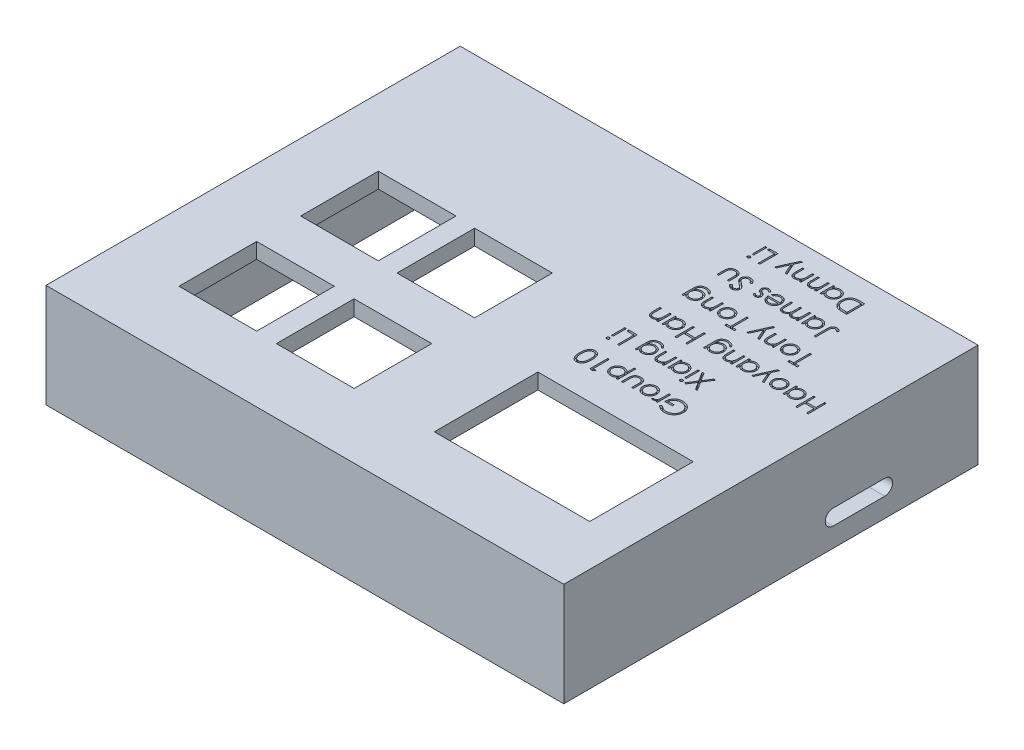
SolidWorks part; units mm, degrees
ref_plane "Front Plane" through (0, 0, 0) normal (0, 0, 1) x (1, 0, 0)
ref_plane "Top Plane" through (0, 0, 0) normal (0, 1, 0) x (1, 0, 0)
ref_plane "Right Plane" through (0, 0, 0) normal (1, 0, 0) x (0, 0, -1)
sketch "Sketch1" plane through (0, 0, 0) normal (0, 1, 0) x (1, 0, 0)
  line L1 (-50, -40) -> (50, -40)
  line L2 (-50, -40) -> (-50, 40)
  line L3 (-50, 40) -> (50, 40)
  line L4 (50, -40) -> (50, 40)
  line L5 (-50, -40) -> (50, 40) construction
  line L6 (-50, 40) -> (50, -40) construction
  point P0 (0, 0)
  dimension "D1" = 100
  dimension "D2" = 80
extrude "Boss-Extrude1" add sketch "Sketch1" along normal blind 20
sketch "Sketch2" plane through (0, 0, 0) normal (0, -1, 0) x (1, 0, 0)
  line L0 (-50, 40) -> (50, 40) construction
  line L1 (-47, 37) -> (47, 37)
  line L2 (-47, 37) -> (-47, -37)
  line L3 (-47, -37) -> (47, -37)
  line L4 (47, 37) -> (47, -37)
  line L5 (-47, 37) -> (47, -37) construction
  line L6 (-47, -37) -> (47, 37) construction
  line L7 (-50, -40) -> (-50, 40) construction
  point P0 (0, 0)
  dimension "D1" = 3
  dimension "D2" = 3
extrude "Cut-Extrude1" cut sketch "Sketch2" against normal blind 17
sketch "Sketch7" plane through (50, 0, 0) normal (1, 0, 0) x (0, 0, -1)
  line L0 (17, 5.2318) -> (17, 2.8813)
  line L1 (40, 20) -> (40, 0) construction
  line L2 (17, 5.2318) -> (22, 5.2318)
  line L3 (17, 5.2318) -> (12, 5.2318)
  line L4 (22, 5.2318) -> (12, 5.2318) construction
  line L5 (22, 3.7318) -> (12, 3.7318)
  line L6 (22, 6.7318) -> (12, 6.7318)
  arc A0 (22, 3.7318) -> (22, 6.7318) centre (22, 5.2318) ccw
  arc A1 (12, 6.7318) -> (12, 3.7318) centre (12, 5.2318) ccw
  point P2 (17, 4.0565)
  point P5 (17, 5.2318)
  dimension "D1" = 23
  dimension "D2" = 5
  dimension "D3" = 5
  dimension "D4" = 1.5
extrude "Cut-Extrude2" cut sketch "Sketch7" against normal blind 17 contours L6 A1 L5 A0
sketch "Sketch10" plane through (0, 20, 0) normal (0, 1, 0) x (1, 0, 0)
  line L0 (-50, -40) -> (50, -40) construction
  line L1 (42, -7) -> (12, -7)
  line L2 (42, -7) -> (42, -27)
  line L3 (42, -27) -> (12, -27)
  line L4 (12, -7) -> (12, -27)
  line L5 (42, -7) -> (12, -27) construction
  line L6 (42, -27) -> (12, -7) construction
  line L7 (50, -40) -> (50, 40) construction
  point P0 (27, -17)
  dimension "D1" = 23
  dimension "D2" = 23
  dimension "D3" = 30
  dimension "D4" = 20
extrude "Cut-Extrude3" cut sketch "Sketch10" against normal blind 17
sketch "Sketch12" plane through (0, 20, 0) normal (0, 1, 0) x (1, 0, 0)
  line L0 (12, -7) -> (12, -27) construction
  line L1 (-18, -27.5) -> (-3, -27.5)
  line L2 (-18, -27.5) -> (-18, -12.5)
  line L3 (-18, -12.5) -> (-3, -12.5)
  line L4 (-3, -27.5) -> (-3, -12.5)
  line L5 (-18, -27.5) -> (-3, -12.5) construction
  line L6 (-18, -12.5) -> (-3, -27.5) construction
  line L7 (-50, -40) -> (50, -40) construction
  point P0 (-10.5, -20)
  dimension "D1" = 15
  dimension "D2" = 20
  dimension "D3" = 15
  dimension "D4" = 15
extrude "Cut-Extrude4" cut sketch "Sketch12" against normal blind 17
sketch "Sketch13" plane through (0, 20, 0) normal (0, 1, 0) x (1, 0, 0)
  line L1 (-37, -27.3155) -> (-22, -27.3155)
  line L2 (-37, -27.3155) -> (-37, -12.3155)
  line L3 (-37, -12.3155) -> (-22, -12.3155)
  line L4 (-22, -27.3155) -> (-22, -12.3155)
  line L5 (-37, -27.3155) -> (-22, -12.3155) construction
  line L6 (-37, -12.3155) -> (-22, -27.3155) construction
  line L7 (-18, -27.5) -> (-3, -27.5) construction
  point P0 (-29.5, -19.8155)
  point P7 (-10.5, -27.5)
  dimension "D1" = 19
  dimension "D2" = 15
  dimension "D3" = 15
extrude "Cut-Extrude5" cut sketch "Sketch13" against normal blind 17
sketch "Sketch14" plane through (0, 20, 0) normal (0, 1, 0) x (1, 0, 0)
  line L0 (-29.5, -12.3155) -> (-29.5, 3.6845)
  line L1 (-22, -12.3155) -> (-37, -12.3155) construction
  line L3 (-22, 11.1845) -> (-37, 11.1845)
  line L4 (-22, 11.1845) -> (-22, -3.8155)
  line L5 (-22, -3.8155) -> (-37, -3.8155)
  line L6 (-37, 11.1845) -> (-37, -3.8155)
  line L7 (-22, 11.1845) -> (-37, -3.8155) construction
  line L8 (-22, -3.8155) -> (-37, 11.1845) construction
  dimension "D1" = 16
  dimension "D2" = 15
  dimension "D3" = 15
sketch "Sketch15" plane through (0, 20, 0) normal (0, 1, 0) x (1, 0, 0)
  line L0 (-22, -3.8155) -> (-37, 11.1845) construction
  line L1 (-37, 11.1845) -> (-22, 11.1845)
  line L2 (-37, 11.1845) -> (-37, -3.8155)
  line L3 (-37, -3.8155) -> (-22, -3.8155)
  line L4 (-22, 11.1845) -> (-22, -3.8155)
  line L5 (-37, 11.1845) -> (-22, -3.8155) construction
  line L6 (-37, -3.8155) -> (-22, 11.1845) construction
  point P0 (-29.5, 3.6845)
extrude "Cut-Extrude6" cut sketch "Sketch15" against normal blind 17
sketch "Sketch18" plane through (0, 0, -40) normal (0, 0, -1) x (-1, 0, 0)
  line L1 (11.2313, 13.4963) -> (20.2313, 13.4963)
  line L2 (11.2313, 13.4963) -> (11.2313, 9.4963)
  line L3 (11.2313, 9.4963) -> (20.2313, 9.4963)
  line L4 (20.2313, 13.4963) -> (20.2313, 9.4963)
  line L5 (11.2313, 13.4963) -> (20.2313, 9.4963) construction
  line L6 (11.2313, 9.4963) -> (20.2313, 13.4963) construction
  point P0 (15.7313, 11.4963)
  dimension "D1" = 9
  dimension "D2" = 4
extrude "Cut-Extrude7" cut sketch "Sketch18" against normal blind 17
sketch "Sketch20" plane through (0, 20, 0) normal (0, 1, 0) x (1, 0, 0)
  line L0 (-10.5, -12.5) -> (-10.5, 3.5)
  line L1 (-3, -12.5) -> (-18, -12.5) construction
  line L3 (-18.1642, 10.9507) -> (-3.1642, 10.9507)
  line L4 (-18.1642, 10.9507) -> (-18.1642, -4.0493)
  line L5 (-18.1642, -4.0493) -> (-3.1642, -4.0493)
  line L6 (-3.1642, 10.9507) -> (-3.1642, -4.0493)
  line L7 (-18.1642, 10.9507) -> (-3.1642, -4.0493) construction
  line L8 (-18.1642, -4.0493) -> (-3.1642, 10.9507) construction
  point P4 (-10.6642, 3.4507)
  dimension "D1" = 16
  dimension "D2" = 15
  dimension "D3" = 15
extrude "Cut-Extrude8" cut sketch "Sketch20" against normal blind 17 contours L6 L3 L4 L5 region at (-10.6642, 20, -3.4507)
sketch "Sketch24" plane through (0, 20, 0) normal (0, 1, 0) x (1, 0, 0)
  line L0 (12.6123, 2.0238) -> (47.1303, 2.0238) construction
  text T0 "Group10\r\nXiang Li\r\nHaoyang Han\r\nTony Tong\r\nJames Su\r\nDanny Li"
extrude "Cut-Extrude11" cut sketch "Sketch24" against normal blind 0.5
